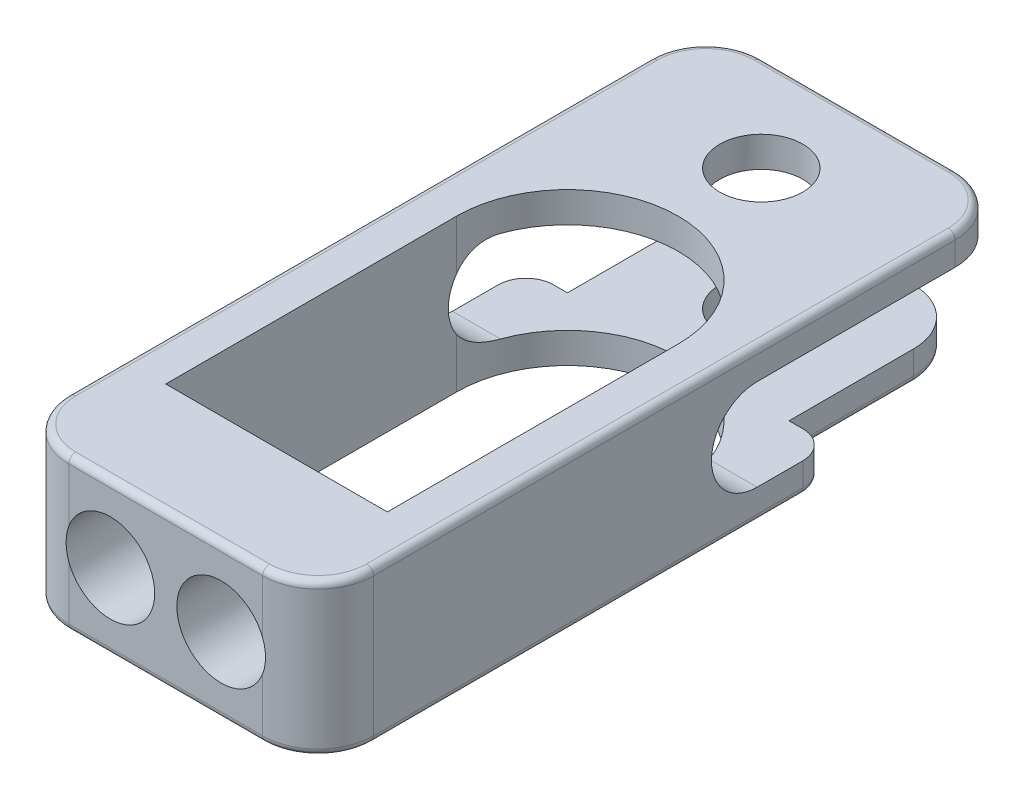
SolidWorks part; units mm, degrees
ref_plane "Alzado" through (0, 0, 0) normal (0, 0, 1) x (1, 0, 0)
ref_plane "Planta" through (0, 0, 0) normal (0, 1, 0) x (1, 0, 0)
ref_plane "Vista lateral" through (0, 0, 0) normal (1, 0, 0) x (0, 0, -1)
sketch "Croquis1" plane through (0, 0, 0) normal (0, 1, 0) x (1, 0, 0)
  line L0 (-8, -17) -> (8, -17)
  line L1 (-7, 25) -> (7, 25)
  line L2 (-11, 21) -> (-11, -21)
  line L3 (-7, -25) -> (7, -25)
  line L4 (11, 21) -> (11, -21)
  line L5 (-11, 25) -> (11, -25) construction
  line L6 (-11, -25) -> (11, 25) construction
  line L7 (-11, -25) -> (11, -25) construction
  line L8 (8, 4) -> (8, -17)
  line L9 (-11, 4) -> (11, 4) construction
  line L10 (0, 25) -> (0, -25) construction
  line L11 (-8, 4) -> (-8, -17)
  line L12 (8, 25) -> (8, -25) construction
  line L13 (-11, -17) -> (11, -17) construction
  line L14 (11, 25) -> (11, -25) construction
  arc A0 (8, 4) -> (-8, 4) centre (0, 4) ccw
  arc A1 (-11, -21) -> (-7, -25) centre (-7, -21) ccw
  arc A2 (7, -25) -> (11, -21) centre (7, -21) ccw
  arc A3 (11, 21) -> (7, 25) centre (7, 21) ccw
  arc A4 (-7, 25) -> (-11, 21) centre (-7, 21) ccw
  point P0 (0, 0)
  point P8 (-8, 25)
  point P9 (-8, -25)
  dimension "D4" = 4
  dimension "D1" = 22
  dimension "D2" = 50
  dimension "D3" = 8
  dimension "D5" = 3
  dimension "D6" = 21
extrude "Saliente-Extruir1" add sketch "Croquis1" against normal blind 11
hole_wizard "Diámetro de taladro Ø6.0 (6)1" positions "Croquis4" profile "Croquis2" hole size "Ø6.0" standard "ISO" end condition through all
sketch "Croquis4" plane through (0, 0, 0) normal (0, 1, 0) x (1, 0, 0)
  arc A0 (8, 4) -> (-8, 4) centre (0, 4) ccw construction
  point P0 (0, 18)
  point P3 (0, 12)
  dimension "D1" = 6
sketch "Croquis2" plane through (0, 0, -18) normal (1, 0, 0) x (0, 0, 1)
  line L0 (0, 0) -> (0, 11)
  line L1 (0, 11) -> (3, 11)
  line L2 (3, 11) -> (3, 0)
  line L5 (3, 0) -> (0, 0)
  line L11 (0, -6.35) -> (0, 107.95) construction
  dimension "Diámetro de taladro hasta el siguiente" = 6
  dimension "Profundidad de taladro hasta el siguiente" = 11
sketch "Croquis5" plane through (11, 0, 0) normal (1, 0, 0) x (0, 0, -1)
  line L0 (-21, -5.5) -> (25, -5.5) construction
  line L1 (-21, -11) -> (-21, 0) construction
  line L2 (25, -11) -> (25, 0) construction
  line L4 (6.7, -2.2) -> (26.0633, -2.2)
  line L5 (6.7, -11) -> (6.7, 0)
  line L6 (6.7, -11) -> (6.7, 0) construction
  line L7 (26.0633, -2.2) -> (26.0633, -8.8)
  line L8 (26.0633, -8.8) -> (6.7, -8.8)
  arc A0 (6.7, -2.2) -> (6.7, -8.8) centre (6.7, -5.5) ccw
  dimension "D1" = 31.7
extrude "Cortar-Extruir1" cut sketch "Croquis5" against normal through all contours L4 L7 L8 A0
sketch "Croquis6" plane through (0, -11, 0) normal (0, -1, 0) x (1, 0, 0)
  line L9 (8, -12) -> (8, -28.4553)
  line L12 (8, -28.4553) -> (12.9339, -28.4553)
  line L13 (12.9339, -28.4553) -> (12.9339, -12)
  line L14 (12.9339, -12) -> (8, -12)
  line L15 (-8, -12) -> (-12.8327, -12)
  line L16 (-12.8327, -12) -> (-12.8327, -28.4553)
  line L17 (-12.8327, -28.4553) -> (-8, -28.4553)
  line L18 (-8, -28.4553) -> (-8, -12)
extrude "Cortar-Extruir5" cut sketch "Croquis6" against normal blind 4
fillet "Redondeo1" radius 4 4 edges at (7, -9.9, -25) (7.504, -8.8, -24.9681) (7.504, -11, -24.9681) (8, -9.9, -24.873)
fillet "Redondeo2" radius 4 4 edges at (-8, -9.9, -24.873) (-7, -9.9, -25) (-7.504, -11, -24.9681) (-7.504, -8.8, -24.9681)
fillet "Redondeo3" radius 2 2 edges at (-11, -9.9, -12) (11, -9.9, -12)
fillet "Redondeo4" radius 0.5 22 edges at (9.8284, 0, 23.8284) (0, 0, 25) (-9.8284, 0, 23.8284) (-11, 0, 0) (-9.8284, 0, -23.8284) (0, 0, -25) (9.8284, 0, -23.8284) (11, 0, 0) (8, -11, -16.5) (6.8284, -11, -23.8284) (0, -11, -25) (-6.8284, -11, -23.8284) (-8.5, -11, -12) (-10.4142, -11, -11.4142) (8.5, -11, -12) (10.4142, -11, -11.4142) (11, -11, 5.5) (9.8284, -11, 23.8284) (0, -11, 25) (-9.8284, -11, 23.8284) (-8, -11, -16.5) (-11, -11, 5.5)
hole_wizard "Diámetro de taladro Ø6.4 (6.4)1" positions "Croquis8" profile "Croquis7" hole size "Ø6.4" standard "ISO" end condition through all
sketch "Croquis8" plane through (0, 0, 25) normal (0, 0, 1) x (1, 0, 0)
  line L0 (11, -10.5) -> (11, -0.5) construction
  point P0 (-4, -5.5)
  point P2 (4, -5.5)
  dimension "D1" = 8
  dimension "D2" = 7
sketch "Croquis7" plane through (-4, -5.5, 25) normal (1, 0, 0) x (0, -1, 0)
  line L0 (0, 0) -> (0, 50)
  line L1 (0, 50) -> (3.2, 50)
  line L2 (3.2, 50) -> (3.2, 0)
  line L5 (3.2, 0) -> (0, 0)
  line L11 (0, -6.35) -> (0, 107.95) construction
  dimension "Diámetro de taladro hasta el siguiente" = 6.4
  dimension "Profundidad de taladro hasta el siguiente" = 50
